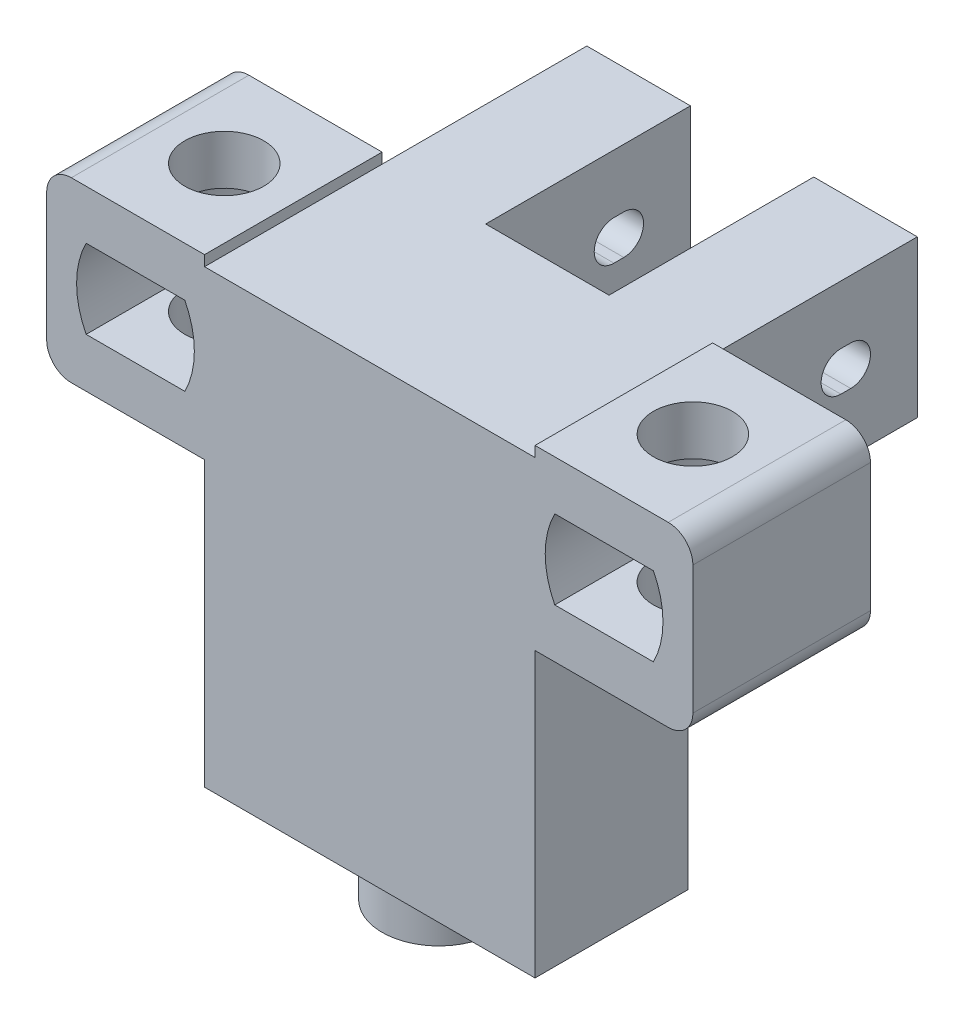
SolidWorks part; units mm, degrees
ref_plane "前视基准面" through (0, 0, 0) normal (0, 0, 1) x (1, 0, 0)
ref_plane "上视基准面" through (0, 0, 0) normal (0, 1, 0) x (1, 0, 0)
ref_plane "右视基准面" through (0, 0, 0) normal (1, 0, 0) x (0, 0, -1)
sketch "草图1" plane through (0, 0, 0) normal (0, 0, 1) x (1, 0, 0)
  line L0 (-14.3113, 0) -> (19.3485, 0) construction
  line L1 (0, 15.0314) -> (0, -18.2179) construction
  line L2 (11.5, -1.6) -> (7.5, -1.6)
  line L3 (-12.1, -3.6) -> (-6.7, -3.6)
  line L4 (-13.1, -2.6) -> (-13.1, 2.6)
  line L5 (-12.1, 3.6) -> (-6.7, 3.6)
  line L6 (13.1, -2.6) -> (13.1, 2.6)
  line L7 (-13.1, -3.6) -> (13.1, 3.6) construction
  line L8 (-13.1, 3.6) -> (13.1, -3.6) construction
  line L9 (-11.5, 1.6) -> (-7.5, 1.6)
  line L11 (-11.5, -1.6) -> (-7.5, -1.6)
  line L13 (-11.5, 1.6) -> (-7.5, -1.6) construction
  line L14 (-11.5, -1.6) -> (-7.5, 1.6) construction
  line L15 (11.5, 1.6) -> (7.5, 1.6)
  line L16 (-6.7, 9.456) -> (-6.7, -6.295) construction
  line L17 (-6.7, 3.6) -> (-6.7, 3.175)
  line L18 (-6.7, 3.175) -> (6.7, 3.175)
  line L19 (6.7, 3.6) -> (6.7, 3.175)
  line L20 (6.7, 3.6) -> (12.1, 3.6)
  line L21 (6.7, -3.6) -> (6.7, -3.175)
  line L22 (-6.7, -3.175) -> (6.7, -3.175)
  line L23 (-6.7, -3.6) -> (-6.7, -3.175)
  line L24 (6.7, -3.6) -> (12.1, -3.6)
  arc A0 (-11.5, 1.6) -> (-11.5, -1.6) centre (-8.3871, 0) ccw
  arc A1 (-7.5, 1.6) -> (-7.5, -1.6) centre (-10.6129, 0) cw
  arc A2 (12.1, -3.6) -> (13.1, -2.6) centre (12.1, -2.6) ccw
  arc A3 (12.1, 3.6) -> (13.1, 2.6) centre (12.1, 2.6) cw
  arc A4 (-13.1, 2.6) -> (-12.1, 3.6) centre (-12.1, 2.6) cw
  arc A5 (-12.1, -3.6) -> (-13.1, -2.6) centre (-12.1, -2.6) cw
  arc A6 (7.5, 1.6) -> (7.5, -1.6) centre (10.6129, 0) ccw
  arc A7 (11.5, 1.6) -> (11.5, -1.6) centre (8.3871, 0) cw
  point P5 (0, 0)
  point P10 (-9.5, 0)
  point P42 (0, 3.175)
  dimension "D6" = 3.5
  dimension "D7" = 3.5
  dimension "D8" = 1
  dimension "D1" = 26.2
  dimension "D2" = 7.2
  dimension "D3" = 19
  dimension "D4" = 3.2
  dimension "D5" = 4
  dimension "D9" = 6.4
  dimension "D10" = 0.425
extrude "凸台-拉伸1" add sketch "草图1" along normal mid plane 7.2
sketch "草图2" plane through (0, 3.6, 0) normal (0, 1, 0) x (1, 0, 0)
  line L0 (-13.7673, 0) -> (16.7342, 0) construction
  line L1 (0, 14.6115) -> (0, -8.15) construction
  line L2 (-6.7, 2.9) -> (-6.7, 11.9)
  line L4 (-6.7, 11.9) -> (-2.5, 11.9)
  line L5 (-2.5, 11.9) -> (-2.5, 2.9)
  line L6 (-2.5, 2.9) -> (2.5, 2.9)
  line L11 (-6.7, -3.6) -> (-12.1, -3.6) construction
  line L12 (2.5, 11.9) -> (2.5, 2.9)
  line L13 (6.7, 11.9) -> (2.5, 11.9)
  line L14 (6.7, 2.9) -> (6.7, 11.9)
  line L15 (-6.7, 2.9) -> (-2.5, 2.9)
  line L16 (2.5, 2.9) -> (6.7, 2.9)
  circle A0 centre (-9.5, 0) radius 1.6
  circle A1 centre (9.5, 0) radius 1.6
  point P22 (0, 2.9)
  line M7 (-6.7, 3.6) -> (-12.1, 3.6)
  dimension "D1" = 3.2
  dimension "D2" = 19
  dimension "D3" = 15.5
  dimension "D4" = 13.4
  dimension "D5" = 5
  dimension "D6" = 9
extrude "凸台-拉伸2" add sketch "草图2" against normal blind 6.35 from offset 0.425 contours L5 L4 L2 M7 | L14 L13 L12 M7 region at (4.6, 3.6, -7.4) region at (-4.6, 3.6, -7.4) offset against normal yes
extrude "切除-拉伸1" cut sketch "草图2<3>" against normal through all both and the other way through all contours A0 | A1 region at (-9.5, 3.6, 0) region at (9.5, 3.6, 0)
sketch "草图2<3>" plane through (0, 3.6, 0) normal (0, 1, 0) x (1, 0, 0) same geometry as "草图2"
sketch "草图5" plane through (0, 0, 3.6) normal (0, 0, 1) x (1, 0, 0)
  line L0 (-16.0105, 0) -> (14.8527, 0) construction
  line L1 (0, 8.1681) -> (0, -18.5223) construction
  line L2 (6.7, -3.175) -> (-6.7, -3.175)
  line L3 (-6.7, -3.175) -> (6.7, -3.175) construction
  line L4 (-6.7, -3.175) -> (-6.7, -15.1)
  line L5 (-6.7, -15.1) -> (6.7, -15.1)
  line L6 (-6.7, 3.6) -> (-12.1, 3.6) construction
  line L7 (6.7, -3.175) -> (6.7, -15.1)
  point P16 (0, -15.1)
  point P17 (0, -3.175)
  dimension "D1" = 18.7
extrude "凸台-拉伸3" add sketch "草图5" against normal blind 6.2
sketch "草图6" plane through (0, -15.1, 0) normal (0, -1, 0) x (1, 0, 0)
  line L0 (-14.9272, 0) -> (18.6004, 0) construction
  line L1 (0, 8.8625) -> (0, -5.8563) construction
  line L2 (-6.7, 3.6) -> (6.7, 3.6) construction
  circle A0 centre (0, 0.8) radius 2.3
  dimension "D1" = 4.6
  dimension "D2" = 2.8
extrude "凸台-拉伸4" add sketch "草图6" along normal blind 2
sketch "草图7" plane through (-6.7, 0, 0) normal (-1, 0, 0) x (0, 0, 1)
  line L0 (-14.8784, 0) -> (8.6315, 0) construction
  line L1 (-9, 6.528) -> (-9, -10.2526) construction
  line L2 (3.6, 2.6) -> (3.6, -2.6) construction
  line L3 (-8.8, 0) -> (-9.2, 0) construction
  line L4 (-8.8, -0.8) -> (-9.2, -0.8)
  line L5 (-8.8, 0.8) -> (-9.2, 0.8)
  arc A0 (-8.8, -0.8) -> (-8.8, 0.8) centre (-8.8, 0) ccw
  arc A1 (-9.2, 0.8) -> (-9.2, -0.8) centre (-9.2, 0) ccw
  point P9 (-9, 0)
  point P14 (-8, 0)
  point P15 (-10, 0)
  dimension "D3" = 0.8
  dimension "D1" = 12.6
  dimension "D2" = 2
extrude "切除-拉伸2" cut sketch "草图7" against normal through all both and the other way through all
